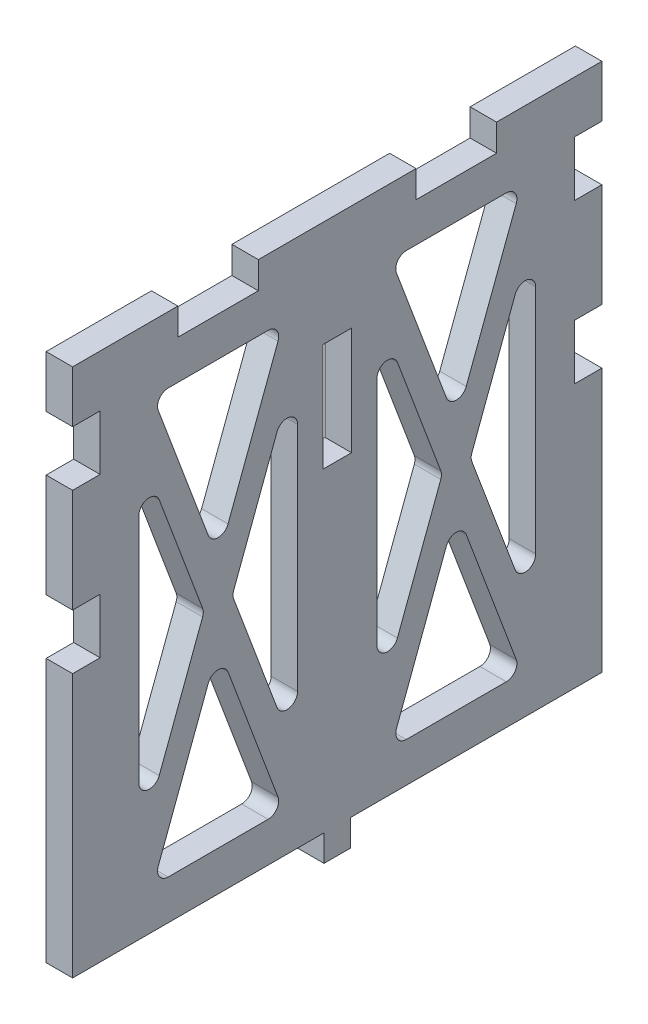
SolidWorks part; units mm, degrees
ref_plane "Front Plane" through (0, 0, 0) normal (0, 0, 1) x (1, 0, 0)
ref_plane "Top Plane" through (0, 0, 0) normal (0, 1, 0) x (1, 0, 0)
ref_plane "Right Plane" through (0, 0, 0) normal (1, 0, 0) x (0, 0, -1)
sketch "Sketch4" plane through (0, 0, 0) normal (1, 0, 0) x (0, 0, -1)
  line L0 (0, 6.35) -> (-60.325, 6.35)
  line L1 (0, 0) -> (6.35, 0)
  line L2 (0, 0) -> (0, 6.35)
  line L3 (0, 6.35) -> (6.35, 6.35) construction
  line L4 (6.35, 0) -> (6.35, 6.35)
  line L5 (6.35, 6.35) -> (66.675, 6.35)
  line L6 (66.675, 6.35) -> (66.675, 69.596)
  line L7 (66.675, 133.35) -> (41.402, 133.35)
  line L8 (-60.325, 133.35) -> (-60.325, 120.904)
  line L9 (3.175, 6.35) -> (3.175, 177.7936) construction
  line L10 (-0.254, 107.95) -> (6.604, 107.95)
  line L11 (0, 107.696) -> (6.35, 107.696) construction
  line L12 (0, 107.696) -> (0, 82.296) construction
  line L13 (0, 82.296) -> (6.35, 82.296) construction
  line L14 (6.35, 107.696) -> (6.35, 82.296) construction
  line L15 (6.604, 107.95) -> (6.604, 82.042)
  line L16 (-0.254, 82.042) -> (6.604, 82.042)
  line L17 (-0.254, 107.95) -> (-0.254, 82.042)
  line L18 (-60.325, 69.85) -> (-53.975, 69.85) construction
  line L19 (-53.975, 69.85) -> (-53.975, 82.55) construction
  line L20 (-53.975, 82.55) -> (-60.325, 82.55) construction
  line L21 (-60.325, 107.95) -> (-53.975, 107.95) construction
  line L22 (-53.975, 107.95) -> (-53.975, 120.65) construction
  line L23 (-53.975, 120.65) -> (-60.325, 120.65) construction
  line L24 (-60.325, 107.696) -> (-60.325, 82.804)
  line L25 (-60.325, 69.596) -> (-60.325, 6.35)
  line L32 (66.675, 120.904) -> (66.675, 133.35)
  line L34 (-60.325, 107.696) -> (-53.721, 107.696)
  line L35 (-53.721, 107.696) -> (-53.721, 120.904)
  line L36 (-53.721, 120.904) -> (-60.325, 120.904)
  line L37 (-60.325, 69.596) -> (-53.721, 69.596)
  line L38 (-53.721, 69.596) -> (-53.721, 82.804)
  line L39 (-53.721, 82.804) -> (-60.325, 82.804)
  line L40 (60.325, 120.65) -> (66.675, 120.65) construction
  line L41 (60.325, 107.95) -> (60.325, 120.65) construction
  line L42 (66.675, 107.95) -> (60.325, 107.95) construction
  line L43 (60.325, 82.55) -> (66.675, 82.55) construction
  line L44 (60.325, 69.85) -> (60.325, 82.55) construction
  line L45 (66.675, 69.85) -> (60.325, 69.85) construction
  line L46 (60.071, 82.804) -> (66.675, 82.804)
  line L47 (60.071, 69.596) -> (60.071, 82.804)
  line L48 (66.675, 69.596) -> (60.071, 69.596)
  line L49 (60.071, 120.904) -> (66.675, 120.904)
  line L50 (60.071, 107.696) -> (60.071, 120.904)
  line L51 (66.675, 107.696) -> (60.071, 107.696)
  line L52 (66.675, 107.696) -> (66.675, 82.804)
  line L53 (-15.748, 133.35) -> (-15.748, 126.873)
  line L59 (-15.875, 133.35) -> (-15.875, 127) construction
  line L60 (-15.875, 127) -> (-34.925, 127) construction
  line L61 (-34.925, 133.35) -> (-34.925, 127) construction
  line L62 (-15.748, 126.873) -> (-35.052, 126.873)
  line L63 (-35.052, 133.35) -> (-35.052, 126.873)
  line L64 (41.402, 133.35) -> (41.402, 126.873)
  line L65 (22.098, 126.873) -> (41.402, 126.873)
  line L66 (22.098, 133.35) -> (22.098, 126.873)
  line L67 (22.098, 133.35) -> (-15.748, 133.35)
  line L68 (-35.052, 133.35) -> (-60.325, 133.35)
  dimension "D1" = 6.35
  dimension "D2" = 6.35
  dimension "D3" = 60.325
  dimension "D4" = 127
  dimension "D5" = 6.35
  dimension "D6" = 25.4
  dimension "D8" = 25.4
  dimension "D9" = 12.7
  dimension "D10" = 12.7
  dimension "D11" = 6.35
  dimension "D12" = 25.4
  dimension "D15" = 25.4
  dimension "D16" = 19.05
  dimension "D17" = 6.35
  dimension "D7" = 0.254
  dimension "D13" = 0.254
  dimension "D14" = 0.254
  dimension "D18" = 0.127
extrude "Boss-Extrude1" add sketch "Sketch4" along normal blind 6.35
sketch "Sketch5" plane through (6.35, 0, 0) normal (1, 0, 0) x (0, 0, -1)
  line L0 (66.675, 6.35) -> (66.675, 69.596) construction
  line L1 (-44.45, 117.475) -> (50.8, 117.475)
  line L2 (-44.45, 117.475) -> (-44.45, 15.875)
  line L3 (-44.45, 15.875) -> (50.8, 15.875)
  line L4 (50.8, 117.475) -> (50.8, 15.875)
  line L5 (66.675, 133.35) -> (41.402, 133.35) construction
  line L6 (-60.325, 133.35) -> (-60.325, 120.904) construction
  line L7 (-60.325, 6.35) -> (0, 6.35) construction
  line L8 (3.175, 117.475) -> (3.175, 15.875) construction
  line L9 (-6.35, 117.475) -> (12.7, 117.475)
  line L10 (-6.35, 117.475) -> (-6.35, 15.875)
  line L11 (-6.35, 15.875) -> (12.7, 15.875)
  line L12 (12.7, 117.475) -> (12.7, 15.875)
  line L13 (12.7, 15.875) -> (50.8, 117.475) construction
  line L14 (9.7272, 16.9898) -> (47.8272, 118.5898)
  line L15 (15.6728, 14.7602) -> (53.7728, 116.3602)
  line L16 (50.8, 15.875) -> (12.7, 117.475) construction
  line L17 (47.8272, 14.7602) -> (9.7272, 116.3602)
  line L18 (53.7728, 16.9898) -> (15.6728, 118.5898)
  line L19 (-6.35, 15.875) -> (-44.45, 117.475) construction
  line L20 (-3.3772, 16.9898) -> (-41.4772, 118.5898)
  line L21 (-9.3228, 14.7602) -> (-47.4228, 116.3602)
  line L22 (-44.45, 15.875) -> (-6.35, 117.475) construction
  line L23 (-41.4772, 14.7602) -> (-3.3772, 116.3602)
  line L24 (-47.4228, 16.9898) -> (-9.3228, 118.5898)
  arc A0 (9.7272, 16.9898) -> (15.6728, 14.7602) centre (12.7, 15.875) ccw
  arc A1 (53.7728, 116.3602) -> (47.8272, 118.5898) centre (50.8, 117.475) ccw
  arc A2 (47.8272, 14.7602) -> (53.7728, 16.9898) centre (50.8, 15.875) ccw
  arc A3 (15.6728, 118.5898) -> (9.7272, 116.3602) centre (12.7, 117.475) ccw
  arc A4 (-3.3772, 16.9898) -> (-9.3228, 14.7602) centre (-6.35, 15.875) cw
  arc A5 (-47.4228, 116.3602) -> (-41.4772, 118.5898) centre (-44.45, 117.475) cw
  arc A6 (-41.4772, 14.7602) -> (-47.4228, 16.9898) centre (-44.45, 15.875) cw
  arc A7 (-9.3228, 118.5898) -> (-3.3772, 116.3602) centre (-6.35, 117.475) cw
  point P18 (31.75, 66.675)
  point P23 (31.75, 66.675)
  point P28 (-25.4, 66.675)
  point P33 (-25.4, 66.675)
  dimension "D6" = 3.175
  dimension "D1" = 15.875
  dimension "D2" = 15.875
  dimension "D3" = 15.875
  dimension "D4" = 9.525
  dimension "D5" = 19.05
extrude "Cut-Extrude1" cut sketch "Sketch5" against normal through all contours L2 L24 L21 | L20 L24 L1 | L23 L20 L10 | L23 L3 L21 | L14 L17 L12 | L18 L14 L1 | L18 L4 L15 | L3 L17 L15 region at (6.35, 103.5558, 25.4) region at (6.35, 66.675, 39.2303) region at (6.35, 66.675, 11.5697) region at (6.35, 29.7942, 25.4) region at (6.35, 103.5558, -31.75) region at (6.35, 66.675, -17.9197) region at (6.35, 66.675, -45.5803) region at (6.35, 29.7942, -31.75)
fillet "Fillet1" radius 2.54 24 edges at (3.175, 57.6326, 25.4) (3.175, 15.875, 9.7409) (3.175, 15.875, 41.0591) (3.175, 108.4326, 6.35) (3.175, 24.9174, 6.35) (3.175, 66.675, 22.0091) (3.175, 57.6326, -31.75) (3.175, 15.875, -47.4091) (3.175, 15.875, -16.0909) (3.175, 66.675, -35.1409) (3.175, 108.4326, -50.8) (3.175, 24.9174, -50.8) (3.175, 66.675, 28.7909) (3.175, 24.9174, 44.45) (3.175, 108.4326, 44.45) (3.175, 117.475, -16.0909) (3.175, 117.475, -47.4091) (3.175, 75.7174, -31.75) (3.175, 117.475, 9.7409) (3.175, 75.7174, 25.4) (3.175, 108.4326, -12.7) (3.175, 66.675, -28.3591) (3.175, 24.9174, -12.7) (3.175, 117.475, 41.0591)
fillet "Fillet2" [suppressed] radius 2.54
